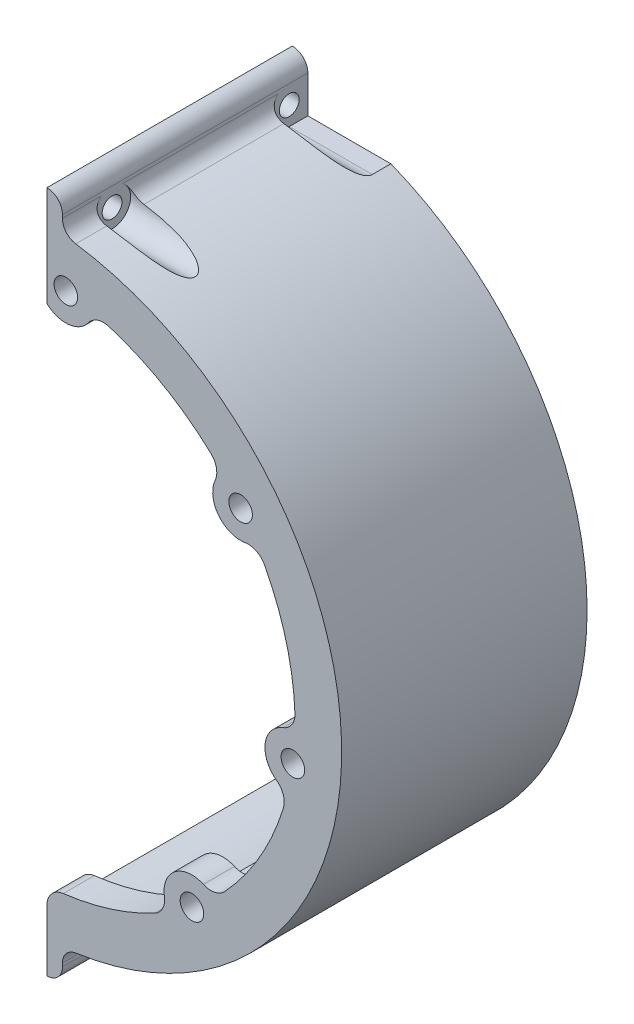
SolidWorks part; units mm, degrees
material "ABS"
ref_plane "前视基准面" through (0, 0, 0) normal (0, 0, 1) x (1, 0, 0)
ref_plane "上视基准面" through (0, 0, 0) normal (0, 1, 0) x (1, 0, 0)
ref_plane "右视基准面" through (0, 0, 0) normal (1, 0, 0) x (0, 0, -1)
sketch "草图1" plane through (0, 0, 0) normal (0, 0, 1) x (1, 0, 0)
  line L0 (0, 0) -> (0, 50)
  line L1 (0, 0) -> (0, -50)
  arc A0 (0, -50) -> (0, 50) centre (0, 0) ccw
extrude "凸台-拉伸1" add sketch "草图1" along normal blind 5
sketch "草图2" plane through (0, 0, 0) normal (0, 0, -1) x (-1, 0, 0)
  line L0 (0, 46) -> (0, 50)
  line L1 (0, -46) -> (0, -50)
  arc A0 (0, 50) -> (0, -50) centre (0, 0) ccw
  arc A1 (0, 46) -> (0, -46) centre (0, 0) ccw
extrude "凸台-拉伸2" add sketch "草图2" along normal blind 34.55
sketch "草图3" plane through (0, 0, 5) normal (0, 0, 1) x (1, 0, 0)
  line L1 (2.5, -50) -> (2.5, 50)
  line L2 (2.5, 50) -> (0, 50)
  line L3 (0, 50) -> (0, -50)
  line L4 (2.5, -50) -> (0, -50)
extrude "切除-拉伸1" cut sketch "草图3" against normal blind 41
sketch "草图4" plane through (0, 0, 5) normal (0, 0, 1) x (1, 0, 0)
  circle A0 centre (0, 0) radius 38
extrude "切除-拉伸2" cut sketch "草图4" against normal blind 5
sketch "草图5" plane through (0, 0, 5) normal (0, 0, 1) x (1, 0, 0)
  line L6 (2.75, 0) -> (-2.75, 0) construction
  line L7 (5, -52.5) -> (5, -51.9615)
  line L8 (2.5, 55) -> (2.5, 49.9375)
  line L9 (5, 52.5) -> (5, 51.9615)
  line L10 (2.5, -55) -> (2.5, -49.9375)
  line L12 (2.5, 49.9375) -> (7.1429, 49.4872)
  line L13 (2.5, -49.9375) -> (7.1429, -49.4872)
  arc A11 (5, 51.9615) -> (7.1429, 49.4872) centre (7.5, 51.9615) ccw
  arc A12 (5, 52.5) -> (2.5, 55) centre (2.5, 52.5) ccw
  arc A15 (5, -52.5) -> (2.5, -55) centre (2.5, -52.5) cw
  arc A16 (5, -51.9615) -> (7.1429, -49.4872) centre (7.5, -51.9615) cw
extrude "凸台-拉伸3" add sketch "草图5" against normal up to surface (39.55 mm away) up to face at (25.25, 0, -34.55)
sketch "草图6" plane through (0, 0, 5) normal (0, 0, 1) x (1, 0, 0)
  circle A1 centre (33.7175, 25.8724) radius 1.9
  circle A2 centre (5.5474, 42.1364) radius 1.9
  circle A8 centre (42.1364, -5.5474) radius 1.9
  circle A9 centre (25.8724, -33.7175) radius 1.9
  circle A10 centre (-5.5474, -42.1364) radius 1.9
  circle A11 centre (-33.7175, -25.8724) radius 1.9
  circle A12 centre (-42.1364, 5.5474) radius 1.9
  circle A13 centre (-25.8724, 33.7175) radius 1.9
  point P19 (0, 0)
  dimension "D1" = 8
extrude "切除-拉伸3" cut sketch "草图6" against normal blind 10
sketch "草图7" plane through (2.5, 0, 0) normal (-1, 0, 0) x (0, 0, 1)
  circle A0 centre (-3, 49.5) radius 1.6
  circle A1 centre (-31.55, 49.5) radius 1.6
  circle A2 centre (-31.55, -49.5) radius 1.6
  circle A3 centre (-3, -49.5) radius 1.6
extrude "切除-拉伸4" cut sketch "草图7" against normal through all
sketch "草图9" plane through (2.5, 0, 0) normal (-1, 0, 0) x (0, 0, 1)
  line L0 (-31.55, 52.5) -> (-34.55, 52.5)
  line L1 (-34.55, 55) -> (-34.55, 45.932) construction
  line L2 (-34.55, 52.5) -> (-34.55, 46.5)
  line L3 (-34.55, 46.5) -> (-31.55, 46.5)
  line L4 (-31.55, -46.5) -> (-34.55, -46.5)
  line L5 (-34.55, -45.932) -> (-34.55, -55) construction
  line L6 (-34.55, -46.5) -> (-34.55, -52.5)
  line L7 (-34.55, -52.5) -> (-31.55, -52.5)
  arc A0 (-31.55, 46.5) -> (-31.55, 52.5) centre (-31.55, 49.5) ccw
  circle A1 centre (-3, 49.5) radius 3
  circle A2 centre (-3, -49.5) radius 3
  arc A3 (-31.55, -52.5) -> (-31.55, -46.5) centre (-31.55, -49.5) ccw
extrude "切除-拉伸7" cut sketch "草图9" against normal through all from offset 2.5 offset against normal yes
sketch "草图11" plane through (0, 0, 0) normal (0, 0, -1) x (-1, 0, 0)
  arc A0 (-4.96, 37.6749) -> (-30.1474, 23.1329) centre (0, 0) ccw
  arc A1 (-30.1474, 23.1329) -> (-30.7929, 29.2924) centre (-33.7175, 25.8724) ccw
  arc A2 (-9.9715, 41.3137) -> (-4.96, 37.6749) centre (-5.5474, 42.1364) ccw
  arc A3 (-9.9715, 41.3137) -> (-30.7929, 29.2924) centre (0, 0) ccw
  arc A4 (-2.5, 37.9177) -> (-2.5, -37.9177) centre (0, 0) ccw construction
  circle A5 centre (-33.7175, 25.8724) radius 1.9 construction
  arc A6 (23.1329, 30.1474) -> (-4.96, 37.6749) centre (0, 0) ccw
  arc A7 (-4.96, 37.6749) -> (-1.061, 42.4868) centre (-5.5474, 42.1364) ccw
  arc A8 (22.1622, 36.2641) -> (23.1329, 30.1474) centre (25.8724, 33.7175) ccw
  arc A9 (22.1622, 36.2641) -> (-1.061, 42.4868) centre (0, 0) ccw
  arc A10 (37.6749, 4.96) -> (23.1329, 30.1474) centre (0, 0) ccw
  arc A11 (23.1329, 30.1474) -> (29.2924, 30.7929) centre (25.8724, 33.7175) ccw
  arc A12 (41.3137, 9.9715) -> (37.6749, 4.96) centre (42.1364, 5.5474) ccw
  arc A13 (41.3137, 9.9715) -> (29.2924, 30.7929) centre (0, 0) ccw
  arc A14 (30.1474, -23.1329) -> (37.6749, 4.96) centre (0, 0) ccw
  arc A15 (37.6749, 4.96) -> (42.4868, 1.061) centre (42.1364, 5.5474) ccw
  arc A16 (36.2641, -22.1622) -> (30.1474, -23.1329) centre (33.7175, -25.8724) ccw
  arc A17 (36.2641, -22.1622) -> (42.4868, 1.061) centre (0, 0) ccw
  arc A18 (4.96, -37.6749) -> (30.1474, -23.1329) centre (0, 0) ccw
  arc A19 (30.1474, -23.1329) -> (30.7929, -29.2924) centre (33.7175, -25.8724) ccw
  arc A20 (9.9715, -41.3137) -> (4.96, -37.6749) centre (5.5474, -42.1364) ccw
  arc A21 (9.9715, -41.3137) -> (30.7929, -29.2924) centre (0, 0) ccw
  arc A22 (-23.1329, -30.1474) -> (4.96, -37.6749) centre (0, 0) ccw
  arc A23 (4.96, -37.6749) -> (1.061, -42.4868) centre (5.5474, -42.1364) ccw
  arc A24 (-22.1622, -36.2641) -> (-23.1329, -30.1474) centre (-25.8724, -33.7175) ccw
  arc A25 (-22.1622, -36.2641) -> (1.061, -42.4868) centre (0, 0) ccw
  arc A26 (-37.6749, -4.96) -> (-23.1329, -30.1474) centre (0, 0) ccw
  arc A27 (-23.1329, -30.1474) -> (-29.2924, -30.7929) centre (-25.8724, -33.7175) ccw
  arc A28 (-41.3137, -9.9715) -> (-37.6749, -4.96) centre (-42.1364, -5.5474) ccw
  arc A29 (-41.3137, -9.9715) -> (-29.2924, -30.7929) centre (0, 0) ccw
  arc A30 (-30.1474, 23.1329) -> (-37.6749, -4.96) centre (0, 0) ccw
  arc A31 (-37.6749, -4.96) -> (-42.4868, -1.061) centre (-42.1364, -5.5474) ccw
  arc A32 (-36.2641, 22.1622) -> (-30.1474, 23.1329) centre (-33.7175, 25.8724) ccw
  arc A33 (-36.2641, 22.1622) -> (-42.4868, -1.061) centre (0, 0) ccw
  point P60 (0, 0)
  arc M10 (-2.5, -37.9177) -> (-2.5, 37.9177) centre (0, 0) cw
  line M14 (-2.5, -45.932) -> (-2.5, -37.9177)
  dimension "D1" = 8
extrude "切除-拉伸8" cut sketch "草图11" against normal blind 10 contours A2 A3 A1 M10 | A32 A33 A31 M10 | A28 A29 A27 M10 | A24 A25 M14 M10 | A6 A7 A9 A8 region at (19.7839, 34.2667, 0) region at (38.2195, 10.2409, 0) region at (34.2667, -19.7839, 0) region at (12.3541, -37.845, 0)
fillet "圆角1" radius 3 8 edges at (2.5, -42.4264, 2.5) (41.3137, -9.9715, 2.5) (29.2924, -30.7929, 2.5) (22.1622, -36.2641, 2.5) (36.2641, 22.1622, 2.5) (42.4868, -1.061, 2.5) (9.9715, 41.3137, 2.5) (30.7929, 29.2924, 2.5)
sketch "草图12" plane through (0, 0, -34.55) normal (0, 0, -1) x (-1, 0, 0)
  line L0 (-2.5, 43.5) -> (0, 0)
  line L1 (21.7525, 0) -> (-21.7525, 0) construction
  line L2 (-2.5, -43.5) -> (-20.2916, -43.5)
  line L3 (-2.5, -43.5) -> (0, 0)
  line L4 (-2.5, 43.5) -> (-20.2916, 43.5)
  arc A0 (-20.2916, 43.5) -> (-20.2916, -43.5) centre (0, 0) ccw
extrude "切除-拉伸9" cut sketch "草图12" against normal up to surface (34.55 mm away) up to face at (27.7724, -33.7175, 0)
